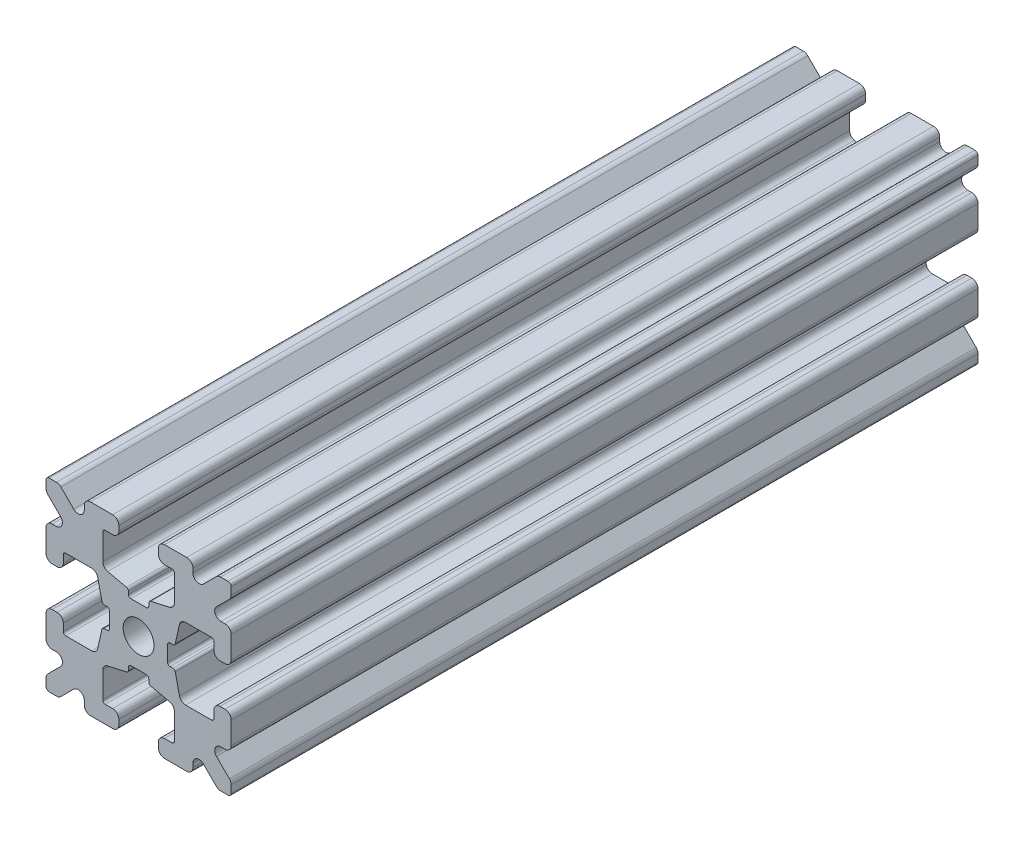
SolidWorks part; units mm, degrees
ref_plane "Front Plane" through (0, 0, 0) normal (0, 0, 1) x (1, 0, 0)
ref_plane "Top Plane" through (0, 0, 0) normal (0, 1, 0) x (1, 0, 0)
ref_plane "Right Plane" through (0, 0, 0) normal (1, 0, 0) x (0, 0, -1)
sketch "Sketch1" plane through (0, 0, 0) normal (0, 0, 1) x (1, 0, 0)
  line L1 (-7.5, -7.5) -> (7.5, -7.5)
  line L2 (-7.5, -7.5) -> (-7.5, 7.5)
  line L3 (-7.5, 7.5) -> (7.5, 7.5)
  line L4 (7.5, -7.5) -> (7.5, 7.5)
  line L5 (-7.5, -7.5) -> (7.5, 7.5) construction
  line L6 (-7.5, 7.5) -> (7.5, -7.5) construction
  circle A0 centre (0, 0) radius 1.25
  point P0 (0, 0)
  dimension "D2" = 2.5
  dimension "D1" = 15
extrude "Boss-Extrude1" add sketch "Sketch1" along normal mid plane 60.5
fillet "Fillet1" radius 0.25 4 edges at (7.5, -7.5, 0) (-7.5, -7.5, 0) (7.5, 7.5, 0) (-7.5, 7.5, 0)
sketch "Sketch2" plane through (0, 0, 30.25) normal (0, 0, 1) x (1, 0, 0)
  line L0 (-7.5, 7.25) -> (-7.5, -7.25) construction
  line L1 (-7.5, 1.6) -> (-6.1, 1.6)
  line L2 (-7.5, 1.6) -> (-7.5, -1.6)
  line L3 (-7.5, -1.6) -> (-6.1, -1.6)
  line L4 (-6.1, 1.6) -> (-6.1, 2.9)
  line L5 (0, 0) -> (-12.1036, 0) construction
  line L6 (-6.1, -2.9) -> (-3.4, -2.9)
  line L7 (0, 0) -> (-7.25, 7.25) construction
  line L8 (-6.1, 2.9) -> (-3.4, 2.9)
  line L9 (-3.4, -2.9) -> (-3.4, 2.9)
  line L10 (55, 0) -> (-55, 0) construction
  line L11 (-6.1, -2.9) -> (-6.1, -1.6)
  line L12 (2.9, 6.1) -> (1.6, 6.1)
  line L13 (2.9, 3.4) -> (-2.9, 3.4)
  line L14 (-2.9, 6.1) -> (-2.9, 3.4)
  line L15 (2.9, 6.1) -> (2.9, 3.4)
  line L16 (-1.6, 6.1) -> (-2.9, 6.1)
  line L17 (1.6, 7.5) -> (1.6, 6.1)
  line L18 (-1.6, 7.5) -> (1.6, 7.5)
  line L19 (-1.6, 7.5) -> (-1.6, 6.1)
  line L20 (-1.6, -7.5) -> (-1.6, -6.1)
  line L21 (-1.6, -7.5) -> (1.6, -7.5)
  line L22 (1.6, -7.5) -> (1.6, -6.1)
  line L23 (-1.6, -6.1) -> (-2.9, -6.1)
  line L24 (2.9, -6.1) -> (2.9, -3.4)
  line L25 (-2.9, -6.1) -> (-2.9, -3.4)
  line L26 (2.9, -3.4) -> (-2.9, -3.4)
  line L27 (2.9, -6.1) -> (1.6, -6.1)
  line L28 (6.1, -2.9) -> (6.1, -1.6)
  line L29 (3.4, -2.9) -> (3.4, 2.9)
  line L30 (6.1, 2.9) -> (3.4, 2.9)
  line L31 (6.1, -2.9) -> (3.4, -2.9)
  line L32 (6.1, 1.6) -> (6.1, 2.9)
  line L33 (7.5, -1.6) -> (6.1, -1.6)
  line L34 (7.5, 1.6) -> (7.5, -1.6)
  line L35 (7.5, 1.6) -> (6.1, 1.6)
  dimension "D1" = 3.2
  dimension "D2" = 5.8
  dimension "D3" = 1.4
  dimension "D4" = 2.7
extrude "Cut-Extrude1" cut sketch "Sketch2" against normal through all
sketch "Sketch4" plane through (0, 0, 30.25) normal (0, 0, 1) x (1, 0, 0)
  line L0 (-3.4, 2.9) -> (-2.75, 0)
  line L1 (55, 0) -> (-55, 0) construction
  line L2 (-2.75, 0) -> (-3.4, -2.9)
  line L3 (-3.4, -2.9) -> (-3.4, 2.9) construction
  line L4 (-3.4, 2.9) -> (-3.4, -2.9)
  line L5 (-2.9, 3.4) -> (0, 2.75)
  line L6 (0, 2.75) -> (2.9, 3.4)
  line L7 (2.9, 3.4) -> (-2.9, 3.4)
  line L8 (3.4, 2.9) -> (2.75, 0)
  line L9 (2.75, 0) -> (3.4, -2.9)
  line L10 (3.4, -2.9) -> (3.4, 2.9)
  line L11 (-2.9, -3.4) -> (0, -2.75)
  line L12 (0, -2.75) -> (2.9, -3.4)
  line L13 (2.9, -3.4) -> (-2.9, -3.4)
  circle A2 centre (0, 0) radius 2.75
  circle A3 centre (0, 0) radius 2.75 construction
  dimension "D1" = 1.5
extrude "Cut-Extrude3" cut sketch "Sketch4" against normal through all
fillet "Fillet3" radius 0.5 16 edges at (-6.1, -1.6, 0) (-7.5, -1.6, 0) (-6.1, 1.6, 0) (-7.5, 1.6, 0) (-1.6, -7.5, 0) (-1.6, -6.1, 0) (1.6, -7.5, 0) (1.6, -6.1, 0) (6.1, -1.6, 0) (7.5, -1.6, 0) (7.5, 1.6, 0) (6.1, 1.6, 0) (1.6, 7.5, 0) (1.6, 6.1, 0) (-1.6, 7.5, 0) (-1.6, 6.1, 0)
fillet "Fillet4" radius 0.5 8 edges at (-3.4, 2.9, 0) (-3.4, -2.9, 0) (2.9, -3.4, 0) (-2.9, -3.4, 0) (3.4, -2.9, 0) (3.4, 2.9, 0) (-2.9, 3.4, 0) (2.9, 3.4, 0)
fillet "Fillet5" radius 3 4 edges at (0, -2.75, 0) (2.75, 0, 0) (-2.75, 0, 0) (0, 2.75, 0)
fillet "Fillet6" radius 0.2 8 edges at (-2.9, -6.1, 0) (2.9, -6.1, 0) (6.1, -2.9, 0) (6.1, 2.9, 0) (2.9, 6.1, 0) (-2.9, 6.1, 0) (-6.1, -2.9, 0) (-6.1, 2.9, 0)
sketch "Sketch5" plane through (0, 0, 30.25) normal (0, 0, 1) x (1, 0, 0)
  line L0 (0, 0) -> (-7.25, 7.25) construction
  line L1 (-7.5, 6.4393) -> (-5.4607, 4.4)
  line L2 (-6.4393, 7.5) -> (-4.4, 5.4607)
  line L3 (-7.5, 4.4) -> (-5.4607, 4.4)
  line L4 (-3.8003, 2.9) -> (-5.9, 2.9) construction
  line L5 (0, 0) -> (-12.1819, 0) construction
  line L6 (-4.4, 7.5) -> (-4.4, 5.4607)
  line L7 (-2.9, 5.9) -> (-2.9, 3.8003) construction
  line L8 (-7.5, 6.4393) -> (-7.5, 4.4)
  line L9 (-7.5, 7.25) -> (-7.5, 2.1) construction
  line L10 (2.1, -7.5) -> (7.25, -7.5) construction
  line L11 (7.5, -7.25) -> (7.5, -2.1) construction
  line L12 (7.25, 7.5) -> (2.1, 7.5) construction
  line L13 (-2.1, 7.5) -> (-7.25, 7.5) construction
  line L14 (-4.4, 7.5) -> (-6.4393, 7.5)
  line L16 (55, 0) -> (-55, 0) construction
  line L17 (0, 0) -> (0, 10.993) construction
  line L18 (0, -54.6431) -> (0, 54.6431) construction
  line L20 (4.4, 7.5) -> (6.4393, 7.5)
  line L22 (7.5, 6.4393) -> (7.5, 4.4)
  line L23 (4.4, 7.5) -> (4.4, 5.4607)
  line L24 (7.5, 4.4) -> (5.4607, 4.4)
  line L25 (6.4393, 7.5) -> (4.4, 5.4607)
  line L26 (7.5, 6.4393) -> (5.4607, 4.4)
  line L27 (7.5, -6.4393) -> (5.4607, -4.4)
  line L28 (6.4393, -7.5) -> (4.4, -5.4607)
  line L29 (7.5, -4.4) -> (5.4607, -4.4)
  line L30 (4.4, -7.5) -> (4.4, -5.4607)
  line L31 (7.5, -6.4393) -> (7.5, -4.4)
  line L33 (4.4, -7.5) -> (6.4393, -7.5)
  line L36 (-4.4, -7.5) -> (-6.4393, -7.5)
  line L38 (-7.5, -6.4393) -> (-7.5, -4.4)
  line L39 (-4.4, -7.5) -> (-4.4, -5.4607)
  line L40 (-7.5, -4.4) -> (-5.4607, -4.4)
  line L41 (-6.4393, -7.5) -> (-4.4, -5.4607)
  line L42 (-7.5, -6.4393) -> (-5.4607, -4.4)
  dimension "D1" = 1.5
  dimension "D2" = 1.5
  dimension "D3" = 1.5
extrude "Cut-Extrude4" cut sketch "Sketch5" against normal through all
fillet "Fillet8" radius 0.5 24 edges at (-5.4607, 4.4, 0) (-7.5, 4.4, 0) (-5.4607, -4.4, 0) (-7.5, -4.4, 0) (-4.4, -7.5, 0) (-4.4, -5.4607, 0) (4.4, -7.5, 0) (4.4, -5.4607, 0) (5.4607, -4.4, 0) (7.5, -4.4, 0) (7.5, 4.4, 0) (5.4607, 4.4, 0) (4.4, 5.4607, 0) (4.4, 7.5, 0) (-4.4, 5.4607, 0) (-4.4, 7.5, 0) (-6.4393, 7.5, 0) (-7.5, 6.4393, 0) (6.4393, 7.5, 0) (7.5, 6.4393, 0) (6.4393, -7.5, 0) (7.5, -6.4393, 0) (-6.4393, -7.5, 0) (-7.5, -6.4393, 0)
sketch "Sketch6" plane through (0, 0, 30.25) normal (0, 0, 1) x (1, 0, 0)
  line L0 (0, 0) -> (0, 11.013) construction
  line L1 (0.6561, 2.8971) -> (2.1235, 2.8971) construction
  line L2 (0, -54.6431) -> (0, 54.6431) construction
  line L3 (0, 0) -> (7.25, 7.25) construction
  line L4 (7.5, 0.8255) -> (7.5, -0.8255)
  line L5 (2.3471, 0.8255) -> (7.5, 0.8255)
  line L6 (0, 0) -> (12.4016, 0) construction
  line L7 (0.8255, -7.5) -> (-0.8255, -7.5)
  line L8 (2.3471, -0.8255) -> (2.3471, 0.8255)
  line L9 (0.8255, -2.3471) -> (0.8255, -7.5)
  line L10 (7.5, -0.8255) -> (2.3471, -0.8255)
  line L11 (-7.5, -0.8255) -> (-2.3471, -0.8255)
  line L12 (-2.3471, -0.8255) -> (-2.3471, 0.8255)
  line L13 (-0.8255, -2.3471) -> (0.8255, -2.3471)
  line L14 (-0.8255, 7.5) -> (-0.8255, 2.3471)
  line L15 (-0.8255, 2.3471) -> (0.8255, 2.3471)
  line L16 (-0.8255, -7.5) -> (-0.8255, -2.3471)
  line L17 (0.8255, 2.3471) -> (0.8255, 7.5)
  line L18 (0.8255, 7.5) -> (-0.8255, 7.5)
  line L19 (3.9, 7.5) -> (2.1, 7.5) construction
  line L20 (-2.3471, 0.8255) -> (-7.5, 0.8255)
  line L21 (-7.5, 0.8255) -> (-7.5, -0.8255)
  point P5 (0, -2.5973)
  point P7 (0, 2.5973)
  dimension "D3" = 0.55
  dimension "D1" = 1.651
extrude "Cut-Extrude5" cut sketch "Sketch6" against normal through all
fillet "Fillet10" radius 0.2 16 edges at (-2.935, 0.8255, 0) (-2.935, -0.8255, 0) (2.935, -0.8255, 0) (2.935, 0.8255, 0) (0.8255, 2.935, 0) (-0.8255, 2.935, 0) (-2.3471, 0.8255, 0) (-2.3471, -0.8255, 0) (0.8255, 2.3471, 0) (-0.8255, 2.3471, 0) (2.3471, 0.8255, 0) (2.3471, -0.8255, 0) (0.8255, -2.935, 0) (0.8255, -2.3471, 0) (-0.8255, -2.3471, 0) (-0.8255, -2.935, 0)
